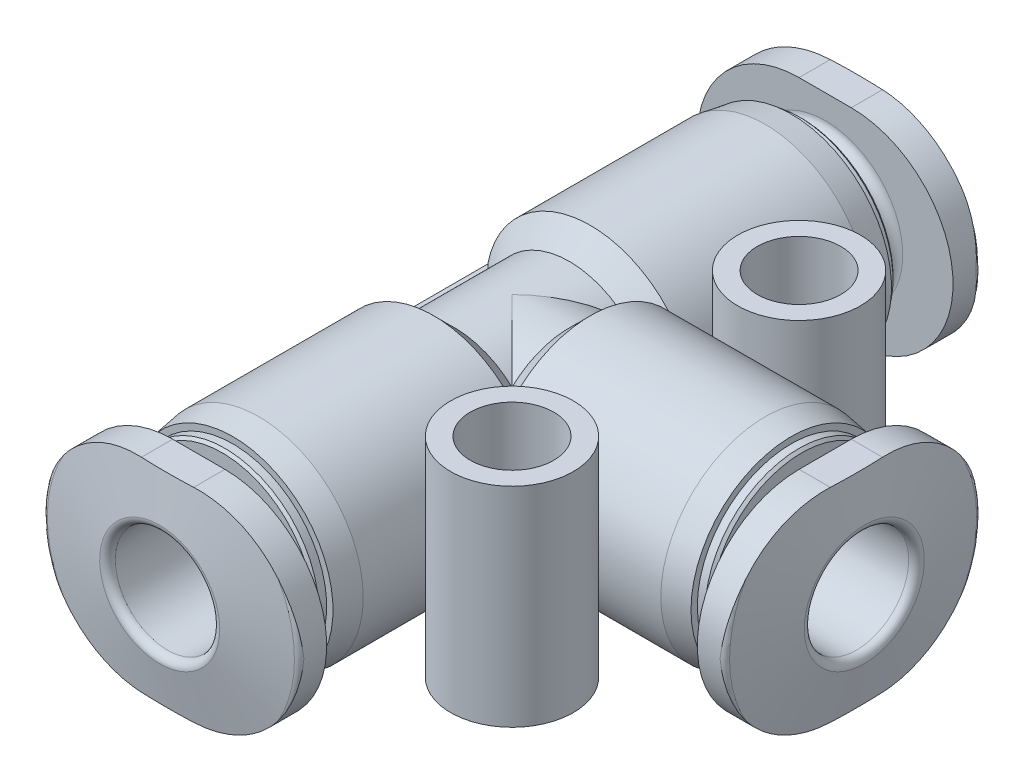
SolidWorks part; units mm, degrees
ref_plane "Front Plane" through (0, 0, 0) normal (0, 0, 1) x (1, 0, 0)
ref_plane "Top Plane" through (0, 0, 0) normal (0, 1, 0) x (1, 0, 0)
ref_plane "Right Plane" through (0, 0, 0) normal (1, 0, 0) x (0, 0, -1)
ref_plane "Plane1" through (0, 0, 0) normal (1, 0, 0) x (0, 0, -1)
sketch "Sketch1" plane through (0, 0, 0) normal (1, 0, 0) x (0, 0, -1)
  line L0 (-13.5, 0) -> (-13.5, 2.3)
  line L1 (-13.5, 2.3) -> (-13.0707, 4.7347)
  line L2 (-12.8737, 4.9) -> (-12, 4.9)
  line L3 (-12, 4.9) -> (-12, 2.975)
  line L4 (-11.625, 2.6) -> (-11.1, 2.6)
  line L5 (-11.1, 2.6) -> (-11.1, 3.5)
  line L6 (-11.1, 3.5) -> (-11, 3.6)
  line L7 (-11, 3.6) -> (-10.7, 3.6)
  line L8 (-10.7, 3.6) -> (-10.7, 3.8416)
  line L9 (-10.7, 3.8416) -> (-9.7, 4)
  line L10 (-9.7, 4) -> (-3, 4)
  line L11 (-3, 4) -> (-2.2, 3.2)
  line L12 (-2.2, 3.2) -> (2.2, 3.2)
  line L13 (2.2, 3.2) -> (3, 4)
  line L14 (3, 4) -> (9.7, 4)
  line L15 (9.7, 4) -> (10.7, 3.8416)
  line L16 (10.7, 3.8416) -> (10.7, 3.6)
  line L17 (10.7, 3.6) -> (11, 3.6)
  line L18 (11, 3.6) -> (11.1, 3.5)
  line L19 (11.1, 3.5) -> (11.1, 2.6)
  line L20 (11.1, 2.6) -> (11.625, 2.6)
  line L21 (12, 2.975) -> (12, 4.9)
  line L22 (12, 4.9) -> (12.8737, 4.9)
  line L23 (13.0707, 4.7347) -> (13.5, 2.3)
  line L24 (13.5, 2.3) -> (13.5, 0)
  line L25 (13.5, 0) -> (-13.5, 0)
  line L26 (13.5, 0) -> (-13.5, 0) construction
  arc A0 (-13.0707, 4.7347) -> (-12.8737, 4.9) centre (-12.8737, 4.7) cw
  arc A1 (-12, 2.975) -> (-11.625, 2.6) centre (-11.625, 2.975) ccw
  arc A2 (11.625, 2.6) -> (12, 2.975) centre (11.625, 2.975) ccw
  arc A3 (12.8737, 4.9) -> (13.0707, 4.7347) centre (12.8737, 4.7) cw
revolve "Revolve1" add sketch "Sketch1" angle 360 about L26
ref_plane "Plane2" through (0, 0, -13.5) normal (0, 0, 1) x (1, 0, 0)
sketch "Sketch2" plane through (0, 0, -13.5) normal (0, 0, 1) x (1, 0, 0)
  line L0 (-20, -20) -> (20, -20)
  line L1 (20, -20) -> (20, 20)
  line L2 (20, 20) -> (-20, 20)
  line L3 (-20, 20) -> (-20, -20)
  line L4 (-1, -3.9) -> (1, -3.9)
  line L5 (1, 3.9) -> (-1, 3.9)
  arc A0 (-1, 3.9) -> (-1, -3.9) centre (-1, 0) ccw
  arc A1 (1, -3.9) -> (1, 3.9) centre (1, 0) ccw
extrude "Cut-Extrude1" cut sketch "Sketch2" along normal blind 1.5
ref_plane "Plane3" through (0, 0, 13.5) normal (0, 0, 1) x (1, 0, 0)
sketch "Sketch3" plane through (0, 0, 13.5) normal (0, 0, 1) x (1, 0, 0)
  line L0 (-20, -20) -> (20, -20)
  line L1 (20, -20) -> (20, 20)
  line L2 (20, 20) -> (-20, 20)
  line L3 (-20, 20) -> (-20, -20)
  line L4 (-1, -3.9) -> (1, -3.9)
  line L5 (1, 3.9) -> (-1, 3.9)
  arc A0 (-1, 3.9) -> (-1, -3.9) centre (-1, 0) ccw
  arc A1 (1, -3.9) -> (1, 3.9) centre (1, 0) ccw
extrude "Cut-Extrude2" cut sketch "Sketch3" against normal blind 1.5
ref_plane "Plane4" through (0, 0, 0) normal (0, 1, 0) x (1, 0, 0)
sketch "Sketch4" plane through (0, 0, 0) normal (0, 1, 0) x (1, 0, 0)
  line L0 (0, 0) -> (0, 3.2)
  line L1 (0, 3.2) -> (2.2, 3.2)
  line L2 (2.2, 3.2) -> (3, 4)
  line L3 (3, 4) -> (9.7, 4)
  line L4 (9.7, 4) -> (10.7, 3.8416)
  line L5 (10.7, 3.8416) -> (10.7, 3.6)
  line L6 (10.7, 3.6) -> (11, 3.6)
  line L7 (11, 3.6) -> (11.1, 3.5)
  line L8 (11.1, 3.5) -> (11.1, 2.6)
  line L9 (11.1, 2.6) -> (11.625, 2.6)
  line L10 (12, 2.975) -> (12, 4.9)
  line L11 (12, 4.9) -> (12.8737, 4.9)
  line L12 (13.0707, 4.7347) -> (13.5, 2.3)
  line L13 (13.5, 2.3) -> (13.5, 0)
  line L14 (13.5, 0) -> (0, 0)
  line L15 (13.5, 0) -> (0, 0) construction
  arc A0 (11.625, 2.6) -> (12, 2.975) centre (11.625, 2.975) ccw
  arc A1 (12.8737, 4.9) -> (13.0707, 4.7347) centre (12.8737, 4.7) cw
revolve "Revolve2" add sketch "Sketch4" angle 360 about L15 reverse direction yes
ref_plane "Plane5" through (13.5, 0, 0) normal (1, 0, 0) x (0, 0, -1)
sketch "Sketch5" plane through (13.5, 0, 0) normal (1, 0, 0) x (0, 0, -1)
  line L0 (-20, -20) -> (20, -20)
  line L1 (20, -20) -> (20, 20)
  line L2 (20, 20) -> (-20, 20)
  line L3 (-20, 20) -> (-20, -20)
  line L4 (-1, -3.9) -> (1, -3.9)
  line L5 (1, 3.9) -> (-1, 3.9)
  arc A0 (-1, 3.9) -> (-1, -3.9) centre (-1, 0) ccw
  arc A1 (1, -3.9) -> (1, 3.9) centre (1, 0) ccw
extrude "Cut-Extrude3" cut sketch "Sketch5" against normal blind 1.5
ref_plane "Plane6" through (0, 0, 0) normal (0, 0, 1) x (1, 0, 0)
sketch "Sketch6" plane through (0, 0, 0) normal (0, 0, 1) x (1, 0, 0)
  line L0 (-3.9291, -0.75) -> (0, -0.75)
  line L1 (0, -0.75) -> (0, 0.75)
  line L2 (0, 0.75) -> (-3.9291, 0.75)
  arc A0 (-3.9291, 0.75) -> (-3.9291, -0.75) centre (0, 0) ccw
extrude "Boss-Extrude1" add sketch "Sketch6" against normal blind 3 and the other way blind 3
ref_plane "Plane7" through (5.5, 0, 0) normal (1, 0, 0) x (0, 0, -1)
sketch "Sketch7" plane through (5.5, 0, 0) normal (1, 0, 0) x (0, 0, -1)
  line L0 (-5.5, -4) -> (-7.85, -4)
  line L1 (-7.85, -4) -> (-7.85, 4)
  line L2 (-7.85, 4) -> (-5.5, 4)
  line L3 (-5.5, 4) -> (-5.5, -4)
  line L4 (-5.5, 4) -> (-5.5, -4) construction
revolve "Revolve3" add sketch "Sketch7" angle 360 about L4 reverse direction yes
ref_plane "Plane8" through (5.5, 0, 0) normal (1, 0, 0) x (0, 0, -1)
sketch "Sketch8" plane through (5.5, 0, 0) normal (1, 0, 0) x (0, 0, -1)
  line L0 (5.5, -4) -> (3.15, -4)
  line L1 (3.15, -4) -> (3.15, 4)
  line L2 (3.15, 4) -> (5.5, 4)
  line L3 (5.5, 4) -> (5.5, -4)
  line L4 (5.5, 4) -> (5.5, -4) construction
revolve "Revolve4" add sketch "Sketch8" angle 360 about L4 reverse direction yes
ref_plane "Plane9" through (5.5, 0, 0) normal (1, 0, 0) x (0, 0, -1)
sketch "Sketch9" plane through (5.5, 0, 0) normal (1, 0, 0) x (0, 0, -1)
  line L0 (-5.5, -4) -> (-7.1, -4)
  line L1 (-7.1, -4) -> (-7.1, 4)
  line L2 (-7.1, 4) -> (-5.5, 4)
  line L3 (-5.5, 4) -> (-5.5, -4)
  line L4 (-5.5, 4) -> (-5.5, -4) construction
revolve "Cut-Revolve1" cut sketch "Sketch9" angle 360 about L4 reverse direction yes
ref_plane "Plane10" through (5.5, 0, 0) normal (1, 0, 0) x (0, 0, -1)
sketch "Sketch10" plane through (5.5, 0, 0) normal (1, 0, 0) x (0, 0, -1)
  line L0 (5.5, -4) -> (3.9, -4)
  line L1 (3.9, -4) -> (3.9, 4)
  line L2 (3.9, 4) -> (5.5, 4)
  line L3 (5.5, 4) -> (5.5, -4)
  line L4 (5.5, 4) -> (5.5, -4) construction
revolve "Cut-Revolve2" cut sketch "Sketch10" angle 360 about L4 reverse direction yes
ref_plane "Plane11" through (0, 0, 0) normal (1, 0, 0) x (0, 0, -1)
sketch "Sketch11" plane through (0, 0, 0) normal (1, 0, 0) x (0, 0, -1)
  line L0 (-13.5, 0) -> (-13.5, 2.3)
  line L1 (-13.2, 2) -> (-2.1, 2)
  line L2 (-2, 1.9) -> (-2, 1.5)
  line L3 (-2, 1.5) -> (2, 1.5)
  line L4 (2, 1.5) -> (2, 1.9)
  line L5 (2.1, 2) -> (13.2, 2)
  line L6 (13.5, 2.3) -> (13.5, 0)
  line L7 (13.5, 0) -> (-13.5, 0)
  line L8 (13.5, 0) -> (-13.5, 0) construction
  arc A0 (-13.5, 2.3) -> (-13.2, 2) centre (-13.2, 2.3) ccw
  arc A1 (-2.1, 2) -> (-2, 1.9) centre (-2.1, 1.9) cw
  arc A2 (2, 1.9) -> (2.1, 2) centre (2.1, 1.9) cw
  arc A3 (13.2, 2) -> (13.5, 2.3) centre (13.2, 2.3) ccw
revolve "Cut-Revolve3" cut sketch "Sketch11" angle 360 about L8 reverse direction yes
ref_plane "Plane12" through (0, 0, 0) normal (0, 1, 0) x (1, 0, 0)
sketch "Sketch12" plane through (0, 0, 0) normal (0, 1, 0) x (1, 0, 0)
  line L0 (0, 0) -> (0, 1.5)
  line L1 (0, 1.5) -> (2, 1.5)
  line L2 (2, 1.5) -> (2, 1.9)
  line L3 (2.1, 2) -> (13.2, 2)
  line L4 (13.5, 2.3) -> (13.5, 0)
  line L5 (13.5, 0) -> (0, 0)
  line L6 (13.5, 0) -> (0, 0) construction
  arc A0 (2, 1.9) -> (2.1, 2) centre (2.1, 1.9) cw
  arc A1 (13.2, 2) -> (13.5, 2.3) centre (13.2, 2.3) ccw
revolve "Cut-Revolve4" cut sketch "Sketch12" angle 360 about L6 reverse direction yes
